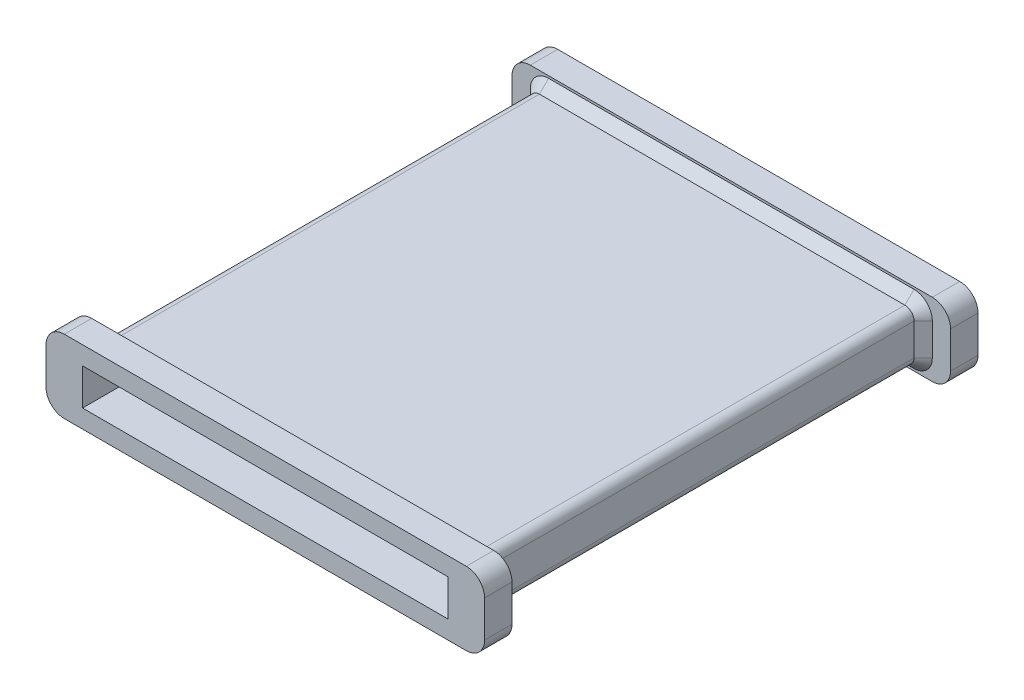
SolidWorks part; units mm, degrees
material "ABS"
ref_plane "Front Plane" through (0, 0, 0) normal (0, 0, 1) x (1, 0, 0)
ref_plane "Top Plane" through (0, 0, 0) normal (0, 1, 0) x (1, 0, 0)
ref_plane "Right Plane" through (0, 0, 0) normal (1, 0, 0) x (0, 0, -1)
sketch "Sketch1" plane through (0, 0, 0) normal (0, 0, 1) x (1, 0, 0)
  line L0 (0, 8) -> (48, 8)
  line L3 (48, 8) -> (48, 0)
  line L4 (48, 0) -> (0, 0)
  line L5 (0, 0) -> (0, 8)
  line L9 (4, 6) -> (44, 6)
  line L10 (4, 6) -> (4, 2)
  line L11 (4, 2) -> (44, 2)
  line L12 (44, 6) -> (44, 2)
  dimension "D1" = 2
  dimension "D2" = 40
  dimension "D4" = 4
  dimension "D5" = 2
  dimension "D7" = 4
  dimension "D8" = 4
extrude "Boss-Extrude1" add sketch "Sketch1" along normal blind 54
sketch "Sketch2" plane through (0, 0, 54) normal (0, 0, 1) x (1, 0, 0)
  line L0 (0, 8) -> (0, 0) construction
  line L1 (4, 6.75) -> (44, 6.75)
  line L2 (3, 5.75) -> (3, 2.25)
  line L3 (4, 1.25) -> (44, 1.25)
  line L4 (45, 5.75) -> (45, 2.25)
  line L5 (4, 2) -> (44, 2) construction
  line L7 (48, 0) -> (48, 8) construction
  arc A0 (3, 2.25) -> (4, 1.25) centre (4, 2.25) ccw
  arc A1 (44, 1.25) -> (45, 2.25) centre (44, 2.25) ccw
  arc A2 (44, 6.75) -> (45, 5.75) centre (44, 5.75) cw
  arc A3 (4, 6.75) -> (3, 5.75) centre (4, 5.75) ccw
  dimension "D1" = 1
  dimension "D2" = 5.5
  dimension "D3" = 3
  dimension "D4" = 3
  dimension "D5" = 0.75
extrude "Cut-Extrude1" cut sketch "Sketch2" against normal offset from surface (48 mm away) 3 from offset 3 flip side to cut up to face at (24, 4, 0) offset against normal yes
fillet "Fillet1" radius 2 8 edges at (48, 8, 52.5) (48, 0, 52.5) (48, 0, 1.5) (48, 8, 1.5) (0, 0, 1.5) (0, 8, 1.5) (0, 0, 52.5) (0, 8, 52.5)
chamfer "Chamfer1" distance 1 angle 45 16 edges at (3, 4, 3) (3.2929, 1.5429, 3) (3.2929, 6.4571, 3) (24, 1.25, 3) (24, 6.75, 3) (44.7071, 1.5429, 3) (44.7071, 6.4571, 3) (45, 4, 3) (24, 1.25, 51) (44.7071, 1.5429, 51) (3.2929, 1.5429, 51) (45, 4, 51) (3, 4, 51) (44.7071, 6.4571, 51) (3.2929, 6.4571, 51) (24, 6.75, 51)
